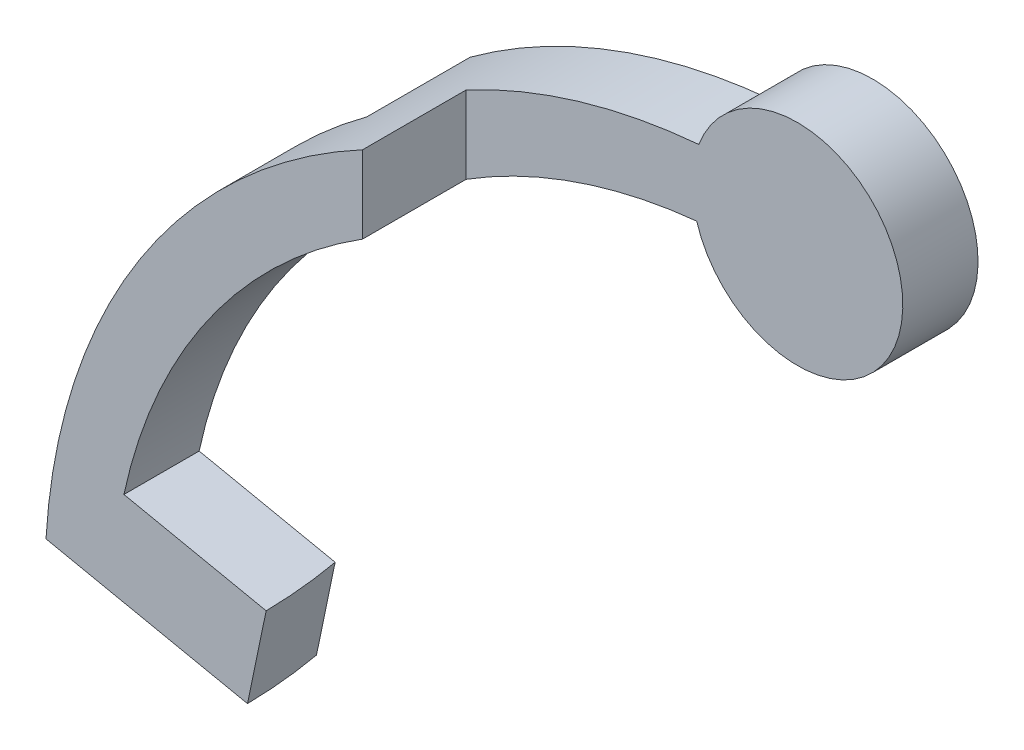
SolidWorks part; units mm, degrees
ref_plane "Front Plane" through (0, 0, 0) normal (0, 0, 1) x (1, 0, 0)
ref_plane "Top Plane" through (0, 0, 0) normal (0, 1, 0) x (1, 0, 0)
ref_plane "Right Plane" through (0, 0, 0) normal (1, 0, 0) x (0, 0, -1)
sketch "Esquisse3" plane through (0, 0, 0) normal (0, 0, 1) x (1, 0, 0)
  line L0 (-43.0597, -35.0596) -> (-29.6704, -37.8465)
  line L1 (-29.6704, -37.8465) -> (-28.4288, -31.8813)
  line L2 (-28.4288, -31.8813) -> (-37.881, -29.9139)
  circle A0 centre (0, 0) radius 7
  arc A1 (-6.5562, 2.4527) -> (-43.0597, -35.0596) centre (-3.1282, -37.4001) ccw
  arc A2 (-37.881, -29.9139) -> (-6.6992, -2.0301) centre (-3.1282, -37.4001) cw
  dimension "D1" = 14
  dimension "D2" = 40
extrude "Boss.-Extru.2" add sketch "Esquisse3" along normal blind 5 contours A0 region at (0, 0, 0)
extrude "Boss.-Extru.3" add sketch "Esquisse3<3>" along normal blind 45 contours L2 A2 A0 A1 L0 L1 region at (-31.4057, -9.8832, 0)
sketch "Esquisse3<3>" plane through (0, 0, 0) normal (0, 0, 1) x (1, 0, 0) same geometry as "Esquisse3"
sketch "Esquisse4" plane through (0, 0, 0) normal (0, 1, 0) x (1, 0, 0)
  line L0 (-6.5562, 0) -> (-6.5562, -5)
  line L4 (-6.5562, -5) -> (-6.5562, 0) construction
  line L6 (-6.5562, -45) -> (-6.5562, -5) construction
  line L8 (-6.5562, -21.6438) -> (-6.5562, -5)
  line L10 (-43.0597, -11.9185) -> (-43.0597, -53.527)
  line L11 (-43.0597, -53.527) -> (-6.4252, -53.527)
  line L12 (-6.4252, -53.527) -> (-6.5562, -21.6438)
  line L13 (-43.0597, -11.9185) -> (-43.0597, -11.8821)
  line L14 (-43.0597, -45) -> (-43.0597, 0) construction
  line L15 (-6.5562, 0) -> (-43.0597, 0) construction
  line L16 (-43.0597, -45) -> (-43.0597, 0)
  line L17 (-6.5562, 0) -> (-43.0597, 0)
  line L18 (-26.7522, 0) -> (-26.7522, -6.8821)
  line L19 (-26.7522, -6.8821) -> (-43.0597, -6.8821)
  line L20 (-43.0597, -6.8821) -> (-43.0597, -11.8821)
  line L21 (-43.0597, -11.8821) -> (-22.0212, -11.8821)
  line L22 (-22.0212, -11.8821) -> (-22.0212, -5)
  line L23 (-22.0212, -5) -> (-6.5562, -5)
  dimension "D2" = 5
extrude "Enlèv. mat.-Extru.3" cut sketch "Esquisse4" against normal through all and the other way blind 5 contours L8 region at (-24.0971, 0, 31.1321)
extrude "Enlèv. mat.-Extru.4" cut sketch "Esquisse4<4>" against normal through all contours L19 L18 L17 L16 region at (-34.906, 0, 3.441)
sketch "Esquisse4<4>" plane through (0, 0, 0) normal (0, 1, 0) x (1, 0, 0) same geometry as "Esquisse4"
sketch "Esquisse5" plane through (-7.5408, -36.229, 0) normal (0.2038, 0.979, 0) x (0.979, -0.2038, 0)
  line L0 (-30.9904, -6.8821) -> (-21.3357, -6.8821) construction
  line L1 (-21.7591, -6.8821) -> (-21.3357, -6.8821)
  line L2 (-21.3357, -6.8821) -> (-21.3357, -11.8821)
  arc A2 (-21.7591, -6.8821) -> (-21.3357, -11.8821) centre (-56.0526, -12.3041) cw
extrude "Enlèv. mat.-Extru.6" cut sketch "Esquisse5" against normal through all
ref_plane "Plan1" through (0, 0, 2.5) normal (0, 0, -1) x (-1, 0, 0)
mirror "Symétrie1" [suppressed] about plane through (0, 0, 2.5) normal (0, 0, -1)
sketch "Esquisse6" [suppressed] plane through (0, 0, 0) normal (0, 1, 0) x (1, 0, 0)
  line L0 (-23.7322, -2.1477) -> (-26.7522, -2)
  line L1 (-26.7522, -2) -> (-43.0597, -2)
  line L2 (-43.0597, -2) -> (-43.0597, -6.9185)
  line L3 (-43.0597, -6.9185) -> (-23.7322, -6.9185)
  line L4 (-23.7322, -6.9185) -> (-23.7322, -2.1477)
extrude "Enlèv. mat.-Extru.7" [suppressed] cut sketch "Esquisse6" against normal through all
